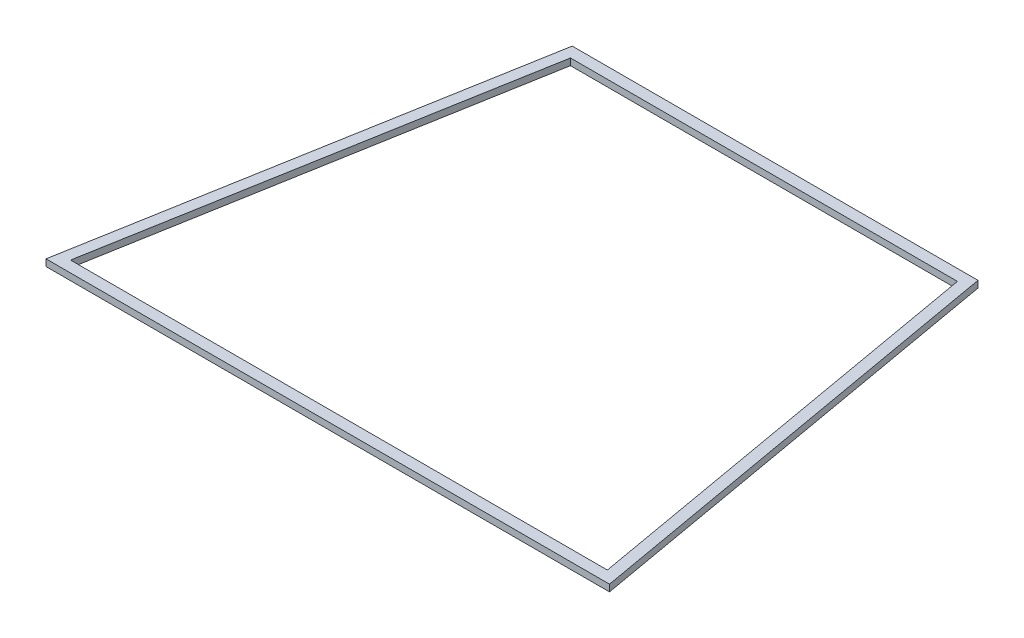
SolidWorks part; units mm, degrees
ref_plane "Front Plane" through (0, 0, 0) normal (0, 0, 1) x (1, 0, 0)
ref_plane "Top Plane" through (0, 0, 0) normal (0, 1, 0) x (1, 0, 0)
ref_plane "Right Plane" through (0, 0, 0) normal (1, 0, 0) x (0, 0, -1)
sketch "Sketch1" plane through (0, 0, 0) normal (0, 1, 0) x (1, 0, 0)
  line L0 (0, 0) -> (33.5021, 190)
  line L3 (240, 0) -> (0, 0)
  line L4 (33.5021, 190) -> (206.4979, 190)
  line L5 (206.4979, 190) -> (240, 0)
  point P4 (0, 0)
  point P7 (108.6452, -0.9007)
  dimension "D1" = 80
  dimension "D2" = 80
  dimension "D3" = 240
  dimension "D4" = 190
extrude "Extrude-Thin1" add sketch "Sketch1" along normal blind 3 thin thin type one direction wall 5
